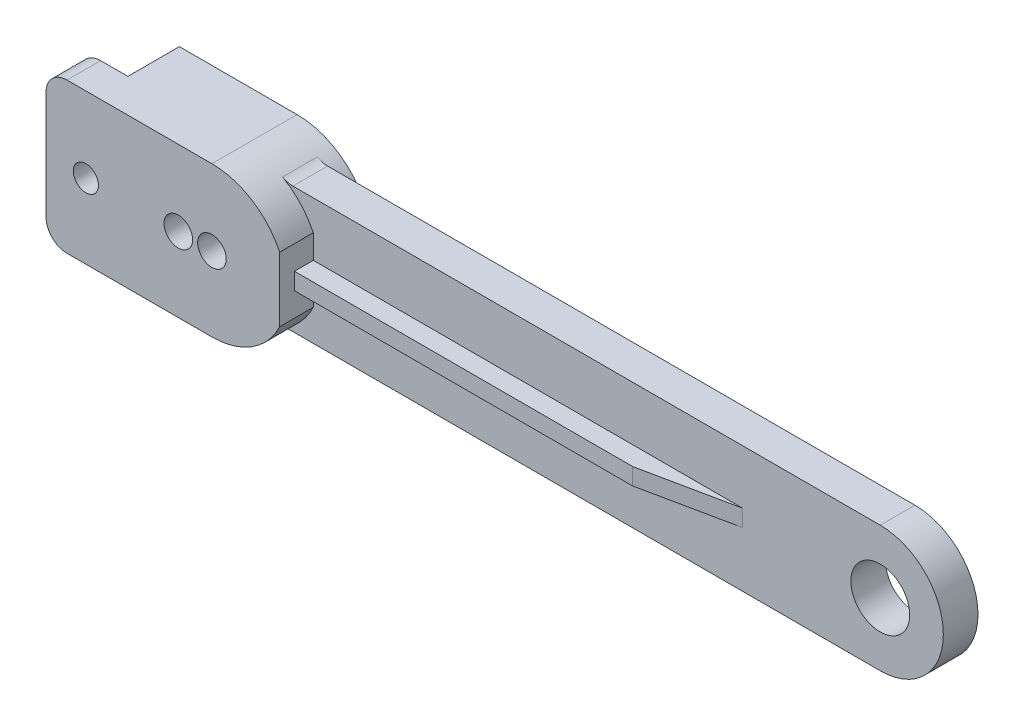
SolidWorks part; units mm, degrees
ref_plane "Front Plane" through (0, 0, 0) normal (0, 0, 1) x (1, 0, 0)
ref_plane "Top Plane" through (0, 0, 0) normal (0, 1, 0) x (1, 0, 0)
ref_plane "Right Plane" through (0, 0, 0) normal (1, 0, 0) x (0, 0, -1)
sketch "Sketch1" plane through (0, 0, 0) normal (0, 0, 1) x (1, 0, 0)
  line L0 (0, 0) -> (14, 0)
  line L1 (14, 7.85) -> (0, 7.85)
  line L2 (0, 7.85) -> (0, 12.85)
  line L3 (0, 12.85) -> (14, 12.85)
  line L4 (14, -5) -> (0, -5)
  line L5 (0, -5) -> (0, 0)
  arc A0 (14, 0) -> (14, 7.85) centre (14, 3.925) ccw
  arc A1 (14, 12.85) -> (14, -5) centre (14, 3.925) cw
  dimension "D1" = 7.85
  dimension "D2" = 14
  dimension "D3" = 5
extrude "Boss-Extrude1" add sketch "Sketch1" along normal blind 4.125
sketch "Sketch2" plane through (0, 0, 0) normal (0, 0, -1) x (-1, 0, 0)
  line L5 (-14, 6.7375) -> (0, 6.7375)
  line L6 (0, -5) -> (0, 0)
  line L7 (0, 0) -> (-14, 0)
  line L8 (-14, 7.85) -> (0, 7.85)
  line L9 (0, 7.85) -> (0, 12.85)
  line L10 (0, 12.85) -> (-14, 12.85)
  line L11 (-14, -5) -> (0, -5)
  line L12 (0, -5) -> (0, 0)
  line L15 (0, 7.85) -> (0, 12.85)
  line L16 (0, 12.85) -> (-14, 12.85)
  line L17 (-14, -5) -> (0, -5)
  line L18 (0, 6.7375) -> (0, 7.85)
  line L19 (-14, 1.1125) -> (0, 1.1125)
  line L20 (0, 1.1125) -> (0, 0)
  arc A1 (-14, 6.7375) -> (-14, 1.1125) centre (-14, 3.925) ccw
  arc A2 (-14, 7.85) -> (-14, 0) centre (-14, 3.925) ccw
  arc A3 (-14, 12.85) -> (-14, -5) centre (-14, 3.925) ccw
  arc A5 (-14, 12.85) -> (-14, -5) centre (-14, 3.925) ccw
  dimension "D2" = 5.625
  dimension "D1" = 0
extrude "Boss-Extrude2" add sketch "Sketch2" along normal blind 2
sketch "Sketch3" plane through (0, 0, 4.125) normal (0, 0, 1) x (1, 0, 0)
  line L1 (0, 12.85) -> (-3.2389, 12.85)
  line L2 (-5.7389, 10.35) -> (-5.7389, -2.5)
  line L3 (-3.2389, -5) -> (0, -5)
  line L6 (0, 0) -> (0, -5)
  line L7 (0, -5) -> (14, -5)
  line L8 (14, 12.85) -> (0, 12.85)
  line L9 (0, 12.85) -> (0, 7.85)
  line L10 (0, 7.85) -> (14, 7.85)
  line L11 (14, 0) -> (0, 0)
  line L13 (0, -5) -> (14, -5)
  line L14 (14, 12.85) -> (0, 12.85)
  line L18 (22.0574, 7.7635) -> (22.0574, 0.0865)
  circle A0 centre (14, 3.8625) radius 1.7
  circle A1 centre (10, 3.8625) radius 1.7
  circle A2 centre (-1, 3.8625) radius 1.5
  arc A3 (22.0574, 7.7635) -> (14, 12.85) centre (14, 3.925) ccw
  arc A4 (14, -5) -> (14, 12.85) centre (14, 3.925) ccw
  arc A5 (14, 0) -> (14, 7.85) centre (14, 3.925) ccw
  arc A6 (14, -5) -> (22.0574, 0.0865) centre (14, 3.925) ccw
  arc A8 (-5.7389, -2.5) -> (-3.2389, -5) centre (-3.2389, -2.5) ccw
  arc A9 (-3.2389, 12.85) -> (-5.7389, 10.35) centre (-3.2389, 10.35) ccw
  dimension "D1" = 3.4
  dimension "D4" = 11
  dimension "D5" = 2.5
  dimension "D2" = 4
  dimension "D3" = 0
extrude "Boss-Extrude3" add sketch "Sketch3" along normal blind 4
sketch "Sketch4" plane through (0, 0, 0) normal (0, 0, 1) x (1, 0, 0)
  line L0 (89.5, 11.3625) -> (18.7216, 11.3625)
  line L1 (89.5, -3.6375) -> (18.7216, -3.6375)
  line L2 (-1, 3.8625) -> (49999, 3.8625) construction
  arc A0 (18.7216, -3.6375) -> (18.7216, 11.3625) centre (14, 3.8625) ccw
  circle A2 centre (-10.5, 3.8625) radius 2.9268 construction
  arc A4 (89.5, 11.3625) -> (89.5, -3.6375) centre (89.5, 3.8625) cw
  dimension "D2" = 100
  dimension "D1" = 15
extrude "Boss-Extrude4" add sketch "Sketch4" along normal up to surface (4.125 mm away) up to face at (22.4912, 3.925, 4.125)
ref_plane "Plane1" through (0, 3.925, 0) normal (0, 1, 0) x (1, 0, 0)
fillet "Fillet2" radius 2.5 2 edges at (18.9335, 11.3625, 2.0625) (18.7396, -3.6375, 2.0625)
sketch "Sketch6" plane through (0, 3.925, 0) normal (0, 1, 0) x (1, 0, 0)
  line L21 (62.2997, -6.3733) -> (73.1167, -4.125)
  line L22 (22.0574, -4.125) -> (60.3227, -4.125)
  line L23 (22.0574, -4.125) -> (22.0574, -6.3733)
  line L24 (22.0574, -6.3733) -> (62.2997, -6.3733)
  line L26 (89.5, -4.125) -> (19.6371, -4.125) construction
  line L27 (60.3227, -4.125) -> (73.1167, -4.125)
  line L28 (22.925, 2) -> (14, 2) construction
  line L29 (21.9765, 2) -> (62.2997, 2)
  line L30 (21.9765, 2) -> (21.9765, 0)
  line L31 (21.9765, 0) -> (73.1167, 0)
  line L33 (89.5, 0) -> (19.6371, 0) construction
  line L34 (62.2997, 2) -> (73.1167, 0)
extrude "Boss-Extrude8" add sketch "Sketch6" along normal mid plane 2
sketch "Sketch9" plane through (0, 0, 4.125) normal (0, 0, 1) x (1, 0, 0)
  circle A0 centre (89.5, 3.8625) radius 3.5
  dimension "D1" = 7
extrude "Cut-Extrude1" cut sketch "Sketch9" against normal through all
